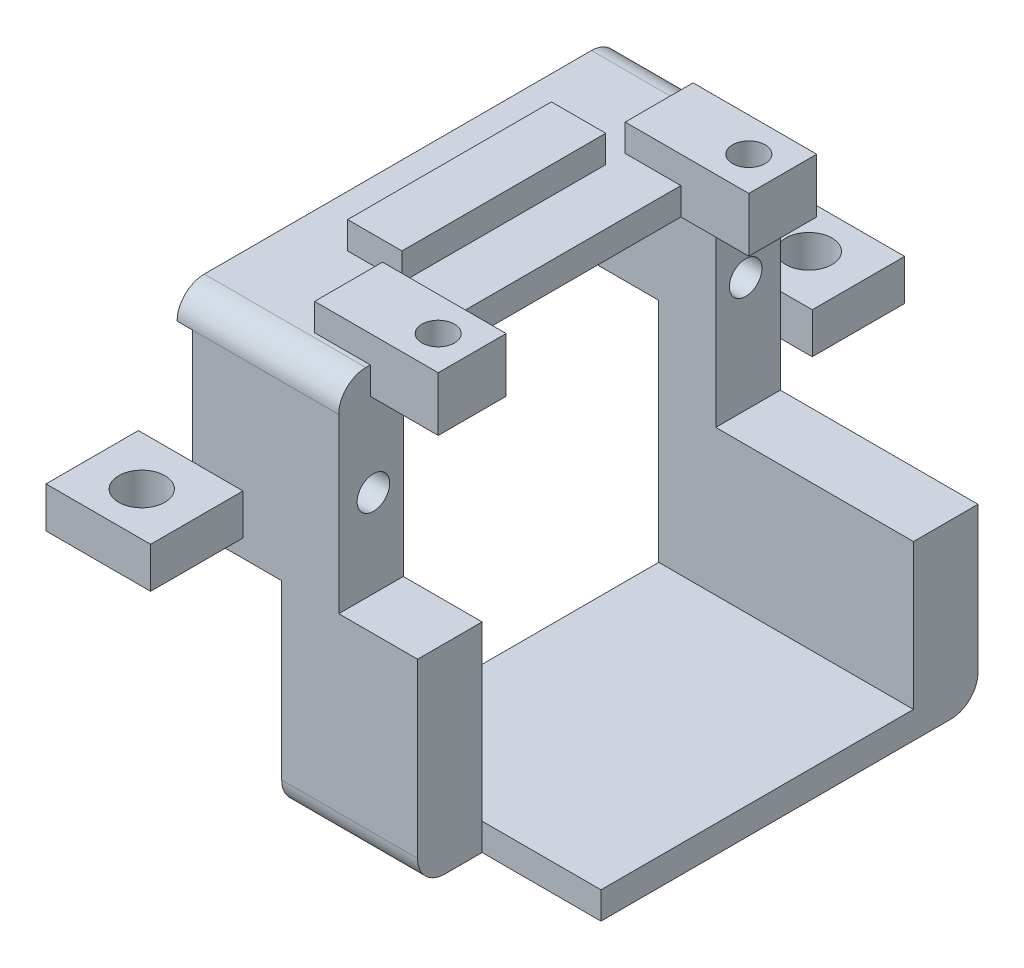
SolidWorks part; units mm, degrees
ref_plane "Front Plane" through (0, 0, 0) normal (0, 0, 1) x (1, 0, 0)
ref_plane "Top Plane" through (0, 0, 0) normal (0, 1, 0) x (1, 0, 0)
ref_plane "Right Plane" through (0, 0, 0) normal (1, 0, 0) x (0, 0, -1)
sketch "Sketch1" plane through (0, 0, 0) normal (0, 1, 0) x (1, 0, 0)
  line L0 (-1.1, 16.25) -> (-1.1, 11.5)
  line L1 (-17.65, -16.25) -> (17.65, -16.25)
  line L2 (-17.65, -16.25) -> (-17.65, 16.25)
  line L3 (-17.65, 16.25) -> (17.65, 16.25)
  line L4 (17.65, -16.25) -> (17.65, 16.25)
  line L5 (-17.65, -16.25) -> (17.65, 16.25) construction
  line L6 (-17.65, 16.25) -> (17.65, -16.25) construction
  line L7 (-1.1, 11.5) -> (17.65, 11.5)
  line L8 (-1.1, -16.25) -> (-1.1, -11.5)
  line L9 (-1.1, -11.5) -> (17.65, -11.5)
  line L10 (-1.1, 11.5) -> (-1.1, -11.5) construction
  line L11 (8.9, -11.5) -> (8.9, -16.25)
  line L12 (-8.8, 16.25) -> (-8.8, 11.5)
  line L13 (-8.8, 11.5) -> (-3.8, 11.5)
  line L14 (-3.8, 11.5) -> (-3.8, 16.25)
  line L15 (-3.8, -16.25) -> (-3.8, -11.5)
  line L16 (-3.8, -11.5) -> (-8.8, -11.5)
  line L17 (-8.8, -11.5) -> (-8.8, -16.25)
  line L18 (-8.8, 11.5) -> (-8.8, -11.5)
  line L19 (5.45, 16.25) -> (5.45, 23.05)
  line L20 (5.45, 23.05) -> (-2.25, 23.05)
  line L21 (-2.25, 23.05) -> (-2.25, 16.25)
  line L22 (-11.65, -16.25) -> (-11.65, -23.05)
  line L23 (-11.65, -23.05) -> (-3.95, -23.05)
  line L24 (-3.95, -23.05) -> (-3.95, -16.25)
  line L25 (9.53, -16.25) -> (9.53, -23.05)
  line L26 (9.53, -23.05) -> (17.23, -23.05)
  line L27 (17.23, -23.05) -> (17.23, -16.25)
  line L28 (-1.1, 11.5) -> (-1.1, -11.5)
  circle A0 centre (1.6, 19.85) radius 1.7
  circle A1 centre (13.38, -19.85) radius 1.7
  circle A2 centre (-7.8, -19.85) radius 1.7
  point P0 (0, 0)
  point P11 (-1.1, 0)
  point P31 (1.6, 23.05)
  point P45 (-7.8, -23.05)
  point P48 (13.38, -23.05)
  dimension "D11" = 3.4
  dimension "D18" = 3.4
  dimension "D19" = 3.4
  dimension "D1" = 32.5
  dimension "D2" = 23
  dimension "D3" = 8.75
  dimension "D4" = 10
  dimension "D5" = 16.55
  dimension "D6" = 2.7
  dimension "D7" = 5
  dimension "D8" = 1.6
  dimension "D9" = 7.7
  dimension "D10" = 6.8
  dimension "D12" = 9.85
  dimension "D13" = 31.03
  dimension "D14" = 7.7
  dimension "D15" = 19.85
  dimension "D16" = 7.7
  dimension "D17" = 6.8
  dimension "D20" = 19.85
extrude "Boss-Extrude1" add sketch "Sketch1" against normal blind 2 contours L7 L28 L9 L4 | L0 L7 L4 L3 | L11 L9 L8 L1 region at (8.275, 0, -13.875) region at (8.275, 0, 0) region at (3.9, 0, 13.875)
extrude "Boss-Extrude2" add sketch "Sketch1<3>" along normal blind 12.7 contours L0 L7 L4 L3 | L11 L9 L8 L1 region at (8.275, 0, -13.875) region at (3.9, 0, 13.875)
sketch "Sketch1<3>" plane through (0, 0, 0) normal (0, 1, 0) x (1, 0, 0) same geometry as "Sketch1"
sketch "Sketch3" plane through (0, 0, 0) normal (0, 1, 0) x (1, 0, 0)
  line L0 (3.1, 16.25) -> (3.1, 11.5)
  line L1 (-17.65, 16.25) -> (17.65, 16.25) construction
  line L2 (-1.1, 11.5) -> (17.65, 11.5) construction
  line L3 (3.1, 11.5) -> (-17.65, 11.5)
  line L4 (-17.65, -16.25) -> (-17.65, 16.25) construction
  line L5 (3.1, -16.25) -> (3.1, -11.5)
  line L6 (-17.65, -16.25) -> (17.65, -16.25) construction
  line L7 (-1.1, -11.5) -> (17.65, -11.5) construction
  line L8 (3.1, -11.5) -> (-17.65, -11.5)
  line L9 (3.1, 11.5) -> (3.1, -11.5)
  line L10 (-7.65, -11.5) -> (-7.65, -16.275)
  line L11 (3.1, 16.25) -> (-17.65, 16.25)
  line L12 (-17.65, 16.25) -> (-17.65, 11.5)
  line L13 (-17.65, -11.5) -> (-17.65, -16.25)
  line L14 (-17.65, -16.25) -> (3.1, -16.25)
  line L15 (-8.8, 11.5) -> (-8.8, -11.5)
  line L16 (-8.8, 11.5) -> (-8.8, 16.25)
  line L17 (-8.8, -11.5) -> (-8.8, -16.25)
  dimension "D1" = 20.75
  dimension "D2" = 10
extrude "Boss-Extrude3" add sketch "Sketch3" along normal blind 12.7 from surface contours L11 L12 L3 L0 | L10 L14 L5 L8 region at (-2.85, 0, -13.875) region at (-2.275, 0, 13.875) starting at face at (8.275, 12.7, -13.875)
extrude "Boss-Extrude4" add sketch "Sketch3<3>" along normal blind 2 from surface contours L16 L3 L0 L11 | L3 L15 L8 L9 | L10 L14 L5 L8 | L8 L17 L14 L10 region at (-2.85, 0, -13.875) region at (-2.85, 0, 0) region at (-2.275, 0, 13.875) region at (-8.225, 0, 13.875) starting at face at (-2.275, 25.4, 13.875)
sketch "Sketch3<3>" plane through (0, 0, 0) normal (0, 1, 0) x (1, 0, 0) same geometry as "Sketch3"
sketch "Sketch2" plane through (0, 0, 0) normal (1, 0, 0) x (0, 0, -1)
  line L0 (13.7, 6.45) -> (-13.7, 6.45) construction
  line L1 (-13.7, 19.15) -> (13.7, 19.15) construction
  circle A0 centre (13.7, 6.45) radius 1.2
  circle A1 centre (-13.7, 6.45) radius 1.2
  circle A2 centre (-13.7, 19.15) radius 1.2
  circle A3 centre (13.7, 19.15) radius 1.2
  point P4 (0, 6.45)
  dimension "D1" = 2.4
  dimension "D2" = 2.4
  dimension "D6" = 2.4
  dimension "D7" = 2.4
  dimension "D3" = 27.4
  dimension "D4" = 6.45
  dimension "D5" = 6.45
extrude "Cut-Extrude1" cut sketch "Sketch2" along normal blind 8 from surface contours A1 | A0 region at (0, 6.45, -13.7) region at (0, 6.45, 13.7) starting at face at (-1.1, 5.85, 0)
extrude "Cut-Extrude2" cut sketch "Sketch2<3>" against normal blind 8 from surface contours A3 | A2 region at (0, 19.15, 13.7) region at (0, 19.15, -13.7) starting at face at (3.1, 19.55, 0)
sketch "Sketch2<3>" plane through (0, 0, 0) normal (1, 0, 0) x (0, 0, -1) same geometry as "Sketch2"
extrude "Boss-Extrude5" add sketch "Sketch1<4>" against normal blind 3 from offset 17 contours L20 L21 L3 L19 A0 | L23 L24 L1 L22 A2 region at (-1.675, 0, -16.3527) region at (-4.0527, 0, 19.65)
sketch "Sketch1<4>" plane through (0, 0, 0) normal (0, 1, 0) x (1, 0, 0) same geometry as "Sketch1"
fillet "Fillet1" radius 2 4 edges at (3.9, -2, 16.25) (-2.85, 27.4, 16.25) (8.275, -2, -16.25) (-2.85, 27.4, -16.25)
sketch "Sketch5" plane through (0, 0, 0) normal (0, 1, 0) x (1, 0, 0)
  line L1 (17.65, 16.25) -> (3.1, 16.25)
  line L2 (17.65, 16.25) -> (17.65, 11.5)
  line L3 (17.65, 11.5) -> (3.1, 11.5)
  line L4 (3.1, 16.25) -> (3.1, 11.5)
extrude "Cut-Extrude3" cut sketch "Sketch5" against normal blind 2 from surface starting at face at (10.375, 12.7, -13.875)
sketch "Sketch6" plane through (0, 0, 0) normal (0, 1, 0) x (1, 0, 0)
  line L1 (-8.8, 11.5) -> (-1.1, 11.5)
  line L2 (-8.8, 11.5) -> (-8.8, 16.25)
  line L3 (-8.8, 16.25) -> (-1.1, 16.25)
  line L4 (-1.1, 11.5) -> (-1.1, 16.25)
extrude "Cut-Extrude4" cut sketch "Sketch6" along normal blind 4 from surface starting at face at (-4.95, 12.7, -13.875)
sketch "Sketch7" plane through (0, 0, 0) normal (0, 1, 0) x (1, 0, 0)
  line L0 (5.6, 11.43) -> (5.6, -11.43) construction
  line L2 (3.1, 8.93) -> (8.1, 8.93)
  line L3 (3.1, 8.93) -> (3.1, 13.93)
  line L4 (3.1, 13.93) -> (8.1, 13.93)
  line L5 (8.1, 8.93) -> (8.1, 13.93)
  line L6 (3.1, 8.93) -> (8.1, 13.93) construction
  line L7 (3.1, 13.93) -> (8.1, 8.93) construction
  line L8 (-5, -7.5) -> (-1, -7.5)
  line L9 (3.1, -8.93) -> (8.1, -8.93)
  line L10 (3.1, -8.93) -> (3.1, -13.93)
  line L11 (3.1, -13.93) -> (8.1, -13.93)
  line L12 (8.1, -8.93) -> (8.1, -13.93)
  line L13 (3.1, -8.93) -> (8.1, -13.93) construction
  line L14 (3.1, -13.93) -> (8.1, -8.93) construction
  line L15 (-5, -7.5) -> (-5, 7.5)
  line L16 (3.1, 12.5) -> (3.1, 14.9) construction
  line L17 (-5, 7.5) -> (-1, 7.5)
  line L18 (-1, -7.5) -> (-1, 7.5)
  line L19 (-5, -7.5) -> (-1, 7.5) construction
  line L20 (-5, 7.5) -> (-1, -7.5) construction
  line L22 (3.1, -8.93) -> (-1, -8.93)
  line L23 (3.1, -8.93) -> (3.1, -13.93)
  line L24 (3.1, -13.93) -> (-1, -13.93)
  line L25 (-1, -8.93) -> (-1, -13.93)
  line L26 (3.1, 13.93) -> (-1, 13.93)
  line L27 (3.1, 13.93) -> (3.1, 8.93)
  line L28 (3.1, 8.93) -> (-1, 8.93)
  line L29 (-1, 13.93) -> (-1, 8.93)
  circle A0 centre (5.6, 11.43) radius 1.2
  circle A1 centre (5.6, -11.43) radius 1.2
  point P4 (5.6, 0)
  point P14 (-3, 0)
  dimension "D2" = 2.4
  dimension "D3" = 2.4
  dimension "D1" = 22.86
  dimension "D4" = 4
  dimension "D5" = 5
  dimension "D6" = 5
  dimension "D7" = 5
  dimension "D8" = 5
  dimension "D9" = 15
  dimension "D10" = 3
extrude "Boss-Extrude6" add sketch "Sketch7" along normal blind 2 and the other way blind 2 from surface contours L8 L18 L17 L15 | L26 L29 L18 L28 L3 | L2 L5 L4 L3 A0 | L18 L25 L24 L10 L22 | L12 L9 L10 L11 A1 region at (3.1707, 0, -11.43) region at (1.05, 0, -11.43) region at (-3, 0, 0) region at (5.6, 0, 9.0007) region at (1.05, 0, 11.43) starting at face at (-2.85, 27.4, 0)
